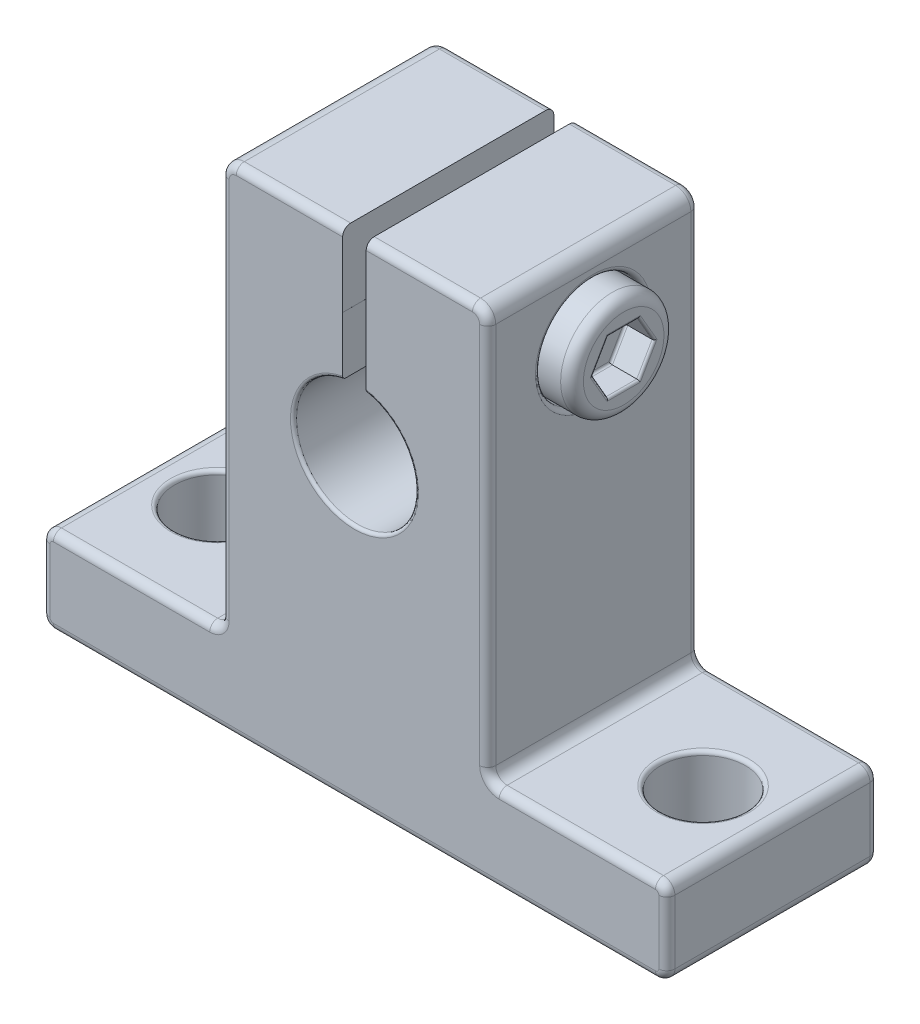
SolidWorks part; units mm, degrees
material "1060 Alloy"
ref_plane "Plano frontal" through (0, 0, 0) normal (0, 0, 1) x (1, 0, 0)
ref_plane "Plano superior" through (0, 0, 0) normal (0, 1, 0) x (1, 0, 0)
ref_plane "Plano direito" through (0, 0, 0) normal (1, 0, 0) x (0, 0, -1)
sketch "Esboço1" plane through (0, 0, 0) normal (0, 0, 1) x (1, 0, 0)
  line L0 (-7.7757, 16.3) -> (-0.7757, 16.3)
  line L1 (-19.815, -16.3) -> (19.815, -16.3)
  line L2 (-20.565, -15.55) -> (-20.565, -11.35)
  line L3 (-19.815, -10.6) -> (-9.5257, -10.6)
  line L4 (20.565, -15.55) -> (20.565, -11.35)
  line L5 (0.7743, 16.3) -> (7.7743, 16.3)
  line L6 (9.5243, -10.6) -> (19.815, -10.6)
  line L7 (8.7743, 15.3) -> (8.7743, -9.85)
  line L8 (-8.7757, 15.3) -> (-8.7757, -9.85)
  line L10 (-0.7757, 11.4644) -> (-0.7757, 16.3)
  line L12 (0.7743, 11.4644) -> (0.7743, 16.3)
  arc A0 (8.7743, 15.3) -> (7.7743, 16.3) centre (7.7743, 15.3) ccw
  arc A1 (-7.7757, 16.3) -> (-8.7757, 15.3) centre (-7.7757, 15.3) ccw
  arc A2 (-20.565, -15.55) -> (-19.815, -16.3) centre (-19.815, -15.55) ccw
  arc A3 (-20.565, -11.35) -> (-19.815, -10.6) centre (-19.815, -11.35) cw
  arc A4 (19.815, -10.6) -> (20.565, -11.35) centre (19.815, -11.35) cw
  arc A5 (19.815, -16.3) -> (20.565, -15.55) centre (19.815, -15.55) ccw
  arc A6 (8.7743, -9.85) -> (9.5243, -10.6) centre (9.5243, -9.85) ccw
  arc A7 (-8.7757, -9.85) -> (-9.5257, -10.6) centre (-9.5257, -9.85) cw
  arc A8 (-0.7757, 11.4644) -> (0.7743, 11.4644) centre (-0.0007, 7.53) ccw
  point P0 (0, 0)
  point P9 (8.7743, 16.3)
  point P15 (-8.7757, 16.3)
  point P18 (-20.565, -16.3)
  point P23 (20.565, -10.6)
  point P26 (20.565, -16.3)
  point P29 (8.7743, -10.6)
  dimension "D1" = 1
  dimension "D4" = 0.75
  dimension "D6" = 8.02
  dimension "D2" = 41.13
  dimension "D3" = 17.55
  dimension "D5" = 5.7
extrude "Ressalto-extrusão1" add sketch "Esboço1" along normal blind 13.9
fillet "Filete2" radius 0.53 34 edges at (-4.2757, 16.3, 13.9) (-8.4828, 16.0071, 13.9) (4.2743, 16.3, 13.9) (8.4814, 16.0071, 13.9) (8.7743, 2.725, 13.9) (8.994, -10.3803, 13.9) (14.6697, -10.6, 13.9) (20.3453, -10.8197, 13.9) (20.565, -13.45, 13.9) (20.3453, -16.0803, 13.9) (0, -16.3, 13.9) (-20.3453, -16.0803, 13.9) (-20.565, -13.45, 13.9) (-20.3453, -10.8197, 13.9) (-14.6703, -10.6, 13.9) (-8.9954, -10.3803, 13.9) (-4.2757, 16.3, 0) (-8.4828, 16.0071, 0) (4.2743, 16.3, 0) (8.4814, 16.0071, 0) (8.7743, 2.725, 0) (8.994, -10.3803, 0) (14.6697, -10.6, 0) (20.3453, -10.8197, 0) (20.565, -13.45, 0) (20.3453, -16.0803, 0) (0, -16.3, 0) (-20.3453, -16.0803, 0) (-20.565, -13.45, 0) (-20.3453, -10.8197, 0) (-14.6703, -10.6, 0) (-8.9954, -10.3803, 0) (-8.7757, 2.725, 13.9) (-8.7757, 2.725, 0)
sketch "Esboço9" plane through (0, 0, 0) normal (0, 0, -1) x (-1, 0, 0)
  circle A1 centre (0.0007, 7.53) radius 4.01
extrude "Ressalto-extrusão4" add sketch "Esboço9" against normal blind 13.9
sketch "Esboço10" plane through (0, 0, 13.9) normal (0, 0, 1) x (1, 0, 0)
  line L0 (-0.7743, 16.3) -> (-0.7743, 7.6345)
  line L1 (0.7743, 11.4644) -> (0.7743, 7.6345)
  line L2 (19.815, -16.3) -> (-19.815, -16.3) construction
  line L3 (-0.7743, 16.3) -> (0.7743, 16.3)
  line L4 (0.7743, 11.4644) -> (0.7743, 16.3)
  line L5 (0.7743, 11.4644) -> (0.7743, 16.3)
  line L8 (0.7743, 11.4644) -> (0.7743, 16.3)
  arc A0 (-0.7743, 7.6345) -> (0.7743, 7.6345) centre (0, 3.7) ccw
  point P7 (0, 0)
  dimension "D1" = 8.02
  dimension "D2" = 20
extrude "Corte-extrusão8" cut sketch "Esboço10" against normal blind 20.9 and the other way blind 16 contours L0 A0 L1 | L4 L3 L0 region at (0, 5.4325, 13.9)
fillet "Filete12" radius 0.2 1 edges at (0, -0.31, 0)
fillet "Filete13" radius 0.2 1 edges at (0, -0.31, 13.9)
sketch "Esboço14" plane through (-8.7757, 0, 0) normal (-1, 0, 0) x (0, 0, 1)
  circle A0 centre (6.95, 11.144) radius 1.71
  dimension "D1" = 3.42
extrude "Corte-extrusão9" cut sketch "Esboço14" against normal blind 20.9
fillet "Filete14" radius 0.2 1 edges at (-8.7757, 9.434, 6.95)
sketch "Esboço15" plane through (8.7743, 0, 0) normal (1, 0, 0) x (0, 0, -1)
  circle A0 centre (-6.95, 11.144) radius 3.5
  dimension "D1" = 7
extrude "Corte-extrusão10" cut sketch "Esboço15" against normal blind 3.9
fillet "Filete16" radius 0.3 1 edges at (8.7743, 14.644, 6.95)
sketch "Esboço16" plane through (4.8743, 0, 0) normal (1, 0, 0) x (0, 0, -1)
  circle A0 centre (-6.95, 11.144) radius 3.4
  dimension "D1" = 6.8
extrude "Ressalto-extrusão5" add sketch "Esboço16" along normal blind 5.9
fillet "Filete19" radius 0.75 2 edges at (4.8743, 14.544, 6.95) (10.7743, 14.544, 6.95)
sketch "Esboço17" plane through (10.7743, 0, 0) normal (1, 0, 0) x (0, 0, -1)
  line L1 (-4.9293, 11.144) -> (-5.9396, 12.894)
  line L2 (-5.9396, 12.894) -> (-7.9604, 12.894)
  line L3 (-7.9604, 12.894) -> (-8.9707, 11.144)
  line L4 (-8.9707, 11.144) -> (-7.9604, 9.394)
  line L5 (-7.9604, 9.394) -> (-5.9396, 9.394)
  line L6 (-5.9396, 9.394) -> (-4.9293, 11.144)
  circle A0 centre (-6.95, 11.144) radius 1.75 construction
  point P1 (-6.95, 9.394)
  dimension "D1" = 3.5
extrude "Corte-extrusão11" cut sketch "Esboço17" against normal blind 1.9
fillet "Filete20" radius 0.15 12 edges at (10.7743, 12.019, 5.4345) (10.7743, 12.894, 6.95) (10.7743, 12.019, 8.4655) (10.7743, 10.269, 8.4655) (10.7743, 9.394, 6.95) (10.7743, 10.269, 5.4345) (8.8743, 9.394, 6.95) (8.8743, 10.269, 8.4655) (8.8743, 12.019, 8.4655) (8.8743, 12.894, 6.95) (8.8743, 12.019, 5.4345) (8.8743, 10.269, 5.4345)
sketch "Esboço18" plane through (4.8743, 0, 0) normal (-1, 0, 0) x (0, 0, 1)
  circle A0 centre (6.95, 11.144) radius 1.7
  dimension "D1" = 3.4
extrude "Ressalto-extrusão6" add sketch "Esboço18" along normal blind 12.9
sketch "Esboço19" plane through (0, -16.3, 0) normal (0, -1, 0) x (1, 0, 0)
  circle A0 centre (-16, 6.95) radius 2.79
  circle A1 centre (16, 6.95) radius 2.79
  dimension "D2" = 5.58
  dimension "D3" = 5.58
  dimension "D1" = 32
extrude "Corte-extrusão12" cut sketch "Esboço19" along normal blind 7.9 and the other way blind 17
fillet "Filete21" radius 0.25 1 edges at (18.79, -10.6, 6.95)
fillet "Filete22" radius 0.25 3 edges at (-16, -16.3, 9.74) (16, -16.3, 9.74) (-16, -10.6, 4.16)
